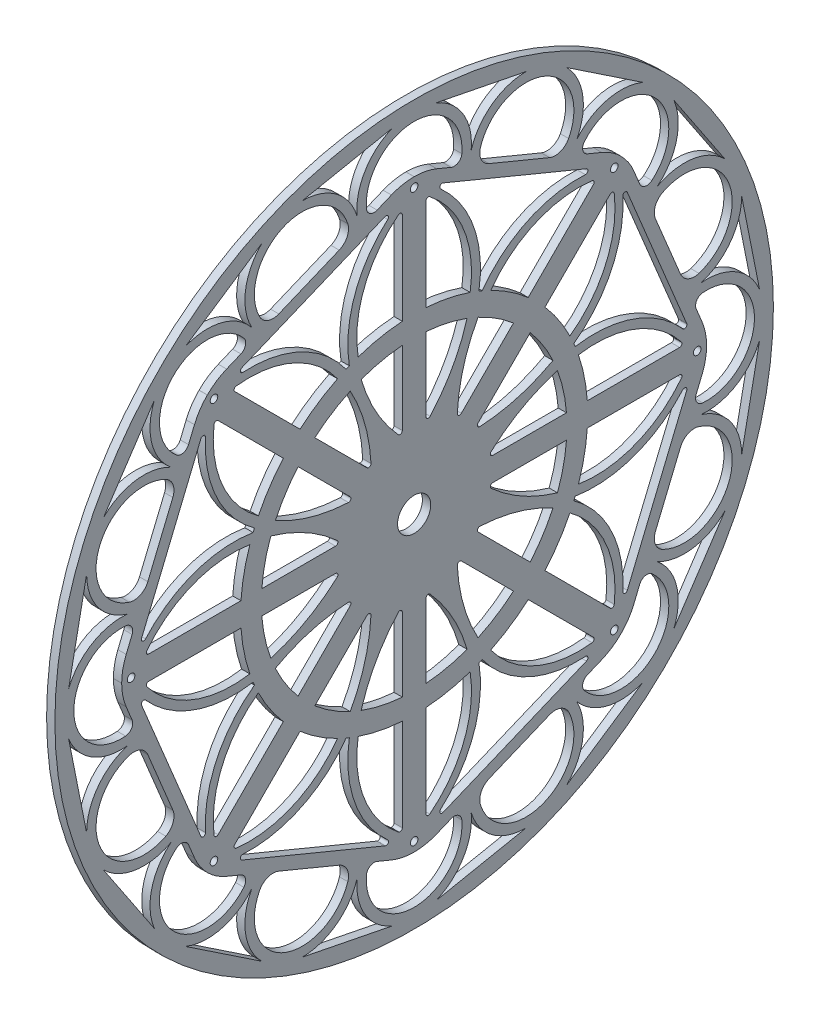
SolidWorks part; units mm, degrees
ref_plane "Front Plane" through (0, 0, 0) normal (1, 0, 0) x (0, 1, 0)
ref_plane "Top Plane" through (0, 0, 0) normal (0, 0, 1) x (0, 1, 0)
ref_plane "Right Plane" through (0, 0, 0) normal (0, 1, 0) x (-1, 0, 0)
sketch "Sketch1" plane through (0, 0, 0) normal (1, 0, 0) x (0, 1, 0)
  line L0 (0, 117.5907) -> (0, 0) construction
  line L1 (83.1492, 83.1492) -> (0, 117.5907) construction
  line L2 (0, 117.5907) -> (-83.1492, 83.1492) construction
  line L4 (-117.5907, 0) -> (-83.1492, -83.1492) construction
  line L5 (-83.1492, -83.1492) -> (0, -117.5907) construction
  line L6 (0, -117.5907) -> (83.1492, -83.1492) construction
  line L7 (83.1492, -83.1492) -> (117.5907, 0) construction
  line L8 (117.5907, 0) -> (83.1492, 83.1492) construction
  line L9 (-83.1492, 83.1492) -> (0, 0) construction
  line L10 (0, 0) -> (-117.5907, 0) construction
  line L11 (-117.5907, 0) -> (-118.1201, 0) construction
  line L12 (-123.5907, 0) -> (-123.5907, 5) construction
  line L14 (-36.2329, 29.1619) -> (-51.4539, 44.3828) construction
  line L15 (-90.9273, 83.8563) -> (-87.3918, 87.3918) construction
  line L16 (-87.3918, 87.3918) -> (-85.6448, 85.6448) construction
  line L18 (-121.1201, 0) -> (-123.5907, 0) construction
  line L19 (-123.5907, 5) -> (-90.9273, 83.8563) construction
  line L20 (-87.1005, 80.0294) -> (-118.1787, 5) construction
  line L21 (-55.2807, 48.2096) -> (-62.699, 30.3003) construction
  line L22 (-59.6103, 24.6914) -> (-36.2329, 29.1619) construction
  line L23 (-67.7667, 5) -> (-51.4539, 44.3828) construction
  line L24 (-59.6103, 24.6914) -> (-46.2411, 5) construction
  line L25 (0, 0) -> (-83.5235, 83.5235)
  line L26 (-55.2807, 48.2096) -> (-84.2721, 77.201) construction
  line L27 (-67.7667, 5) -> (-46.2411, 5) construction
  line L28 (-114.1787, 5) -> (-73.1787, 5) construction
  line L29 (-65.7604, 22.9093) -> (-73.1787, 5) construction
  line L30 (-85.6448, 85.6448) -> (-87.3918, 87.3918)
  line L31 (-83.1492, 83.1492) -> (-88.2348, 70.8713) construction
  line L32 (-87.3918, 87.3918) -> (-90.9273, 83.8563)
  line L33 (-90.9273, 83.8563) -> (-123.5907, 5)
  line L34 (-123.5907, 5) -> (-123.5907, 0)
  line L35 (-123.5907, 0) -> (-121.1201, 0)
  line L36 (-118.1201, 0) -> (0, 0)
  arc A0 (-108.6396, 0) -> (-76.8198, 76.8198) centre (0, 0) ccw construction
  arc A5 (-87.1005, 80.0294) -> (-64.2297, 26.6048) centre (-38.2585, 69.3307) ccw construction
  arc A6 (-114.1787, 5) -> (-65.7604, 22.9093) centre (-76.7606, -21.7561) cw construction
  arc A7 (-84.2721, 77.201) -> (-62.699, 30.3003) centre (-38.8941, 69.6618) ccw construction
  arc A8 (-118.1787, 5) -> (-64.2297, 26.6048) centre (-76.0771, -21.9713) cw construction
  arc A9 (-117.5907, 0) -> (-83.1492, 83.1492) centre (0, 0) ccw construction
  arc A12 (-85.6448, 85.6448) -> (-83.5235, 83.5235) centre (-84.5842, 84.5842) ccw
  arc A13 (-121.1201, 0) -> (-118.1201, 0) centre (-119.6201, 0) cw
  dimension "D1" = 6
  dimension "D8" = 50
  dimension "D9" = 4
  dimension "D12" = 46
  dimension "D13" = 4
  dimension "D4" = 1.5
  dimension "D11" = 1.5
  dimension "D2" = 90
  dimension "D3" = 5
  dimension "D5" = 5
  dimension "D7" = 5
  dimension "D10" = 45
extrude "Boss-Extrude3" add sketch "Sketch1" along normal blind 3.5
sketch "Sketch2" plane through (3.5, 0, 0) normal (1, 0, 0) x (0, 1, 0)
  line L0 (-84.2721, 77.201) -> (-55.2807, 48.2096)
  line L1 (-55.2807, 48.2096) -> (-62.699, 30.3003)
  line L2 (-65.7604, 22.9093) -> (-73.1787, 5)
  line L3 (-73.1787, 5) -> (-114.1787, 5)
  line L4 (-118.1787, 5) -> (-87.1005, 80.0294)
  arc A0 (-87.1005, 80.0294) -> (-64.2297, 26.6048) centre (-38.2585, 69.3307) ccw
  arc A1 (-62.699, 30.3003) -> (-84.2721, 77.201) centre (-38.8941, 69.6618) cw
  arc A2 (-64.2297, 26.6048) -> (-118.1787, 5) centre (-76.0771, -21.9713) ccw
  arc A3 (-65.7604, 22.9093) -> (-114.1787, 5) centre (-76.7606, -21.7561) ccw
extrude "Cut-Extrude5" cut sketch "Sketch2" against normal blind 3.5 contours A2 A0 L4 | A1 L1 L0 | L2 A3 L3 region at (3.5, -71.2812, 52.1242) region at (3.5, -87.2608, 13.5461) region at (3.5, -92.9106, 38.4849)
sketch "Sketch4" plane through (3.5, 0, 0) normal (1, 0, 0) x (0, 1, 0)
  line L0 (0, 0) -> (-83.5235, 83.5235) construction
  line L1 (-67.7667, 5) -> (-51.4539, 44.3828) construction
  line L2 (-118.1201, 0) -> (0, 0) construction
  line L3 (-58.6536, 27.0011) -> (-60.567, 22.3817) construction
  line L5 (-51.4539, 44.3828) -> (-25.2262, 18.1552)
  line L6 (-67.7667, 5) -> (-30.6753, 5)
  line L7 (-51.4539, 44.3828) -> (-58.6536, 27.0011)
  line L8 (-67.7667, 5) -> (-60.567, 22.3817)
  line L9 (-64.2297, 26.6048) -> (-59.6103, 24.6914) construction
  arc A0 (-18.3848, 18.3848) -> (-58.6536, 27.0011) centre (-24.2, 89.6145) cw construction
  arc A1 (-26, 0) -> (-60.567, 22.3817) centre (-80.479, -46.255) ccw construction
  arc A2 (-25.2262, 18.1552) -> (-58.6536, 27.0011) centre (-24.2, 89.6145) cw
  arc A3 (-60.567, 22.3817) -> (-30.6753, 5) centre (-80.479, -46.255) cw
  dimension "D1" = 26
  dimension "D2" = 26
  dimension "D3" = 5
  dimension "D4" = 5
extrude "Cut-Extrude6" cut sketch "Sketch4" against normal up to vertex (3.5 mm away) contours A2 L7 L5 | A3 L6 L8 up to point (0, -46.2411, 5)
fillet "Fillet3" radius 1 6 edges at (1.75, -118.1787, 5) (1.75, -87.1005, 80.0294) (1.75, -30.6753, 5) (1.75, -25.2262, 18.1552) (1.75, -114.1787, 5) (1.75, -84.2721, 77.201)
fillet "Fillet4" radius 25 2 edges at (1.75, -90.9273, 83.8563) (1.75, -123.5907, 5)
pattern_circular "CirPattern2" count 8 over 360 about axis through (3.5, 0, 0) along (-1, 0, 0) of "Boss-Extrude3", "Cut-Extrude5", "Cut-Extrude6", "Fillet3", "Fillet4"
sketch "Sketch5" plane through (3.5, 0, 0) normal (1, 0, 0) x (0, 0, -1)
  line L0 (0.0272, -123.5907) -> (0, -146.4823)
  line L1 (0, -146.4823) -> (0, -151.7532)
  line L2 (-87.411, -87.3726) -> (-103.6014, -103.5559)
  line L3 (-103.6014, -103.5559) -> (-107.3293, -107.2821)
  line L4 (-83.8563, -90.9273) -> (-5, -123.5907) construction
  line L5 (-62.7141, -99.6847) -> (-44.4281, -107.259) construction
  line L6 (-44.4281, -107.259) -> (-26.1422, -114.8333) construction
  line L7 (-87.411, -87.3726) -> (-62.7141, -99.6847) construction
  line L8 (-26.1422, -114.8333) -> (0.0272, -123.5907) construction
  line L9 (-103.6014, -103.5559) -> (-87.5988, -117.4032) construction
  line L10 (-21.1068, -144.9537) -> (0, -146.4823) construction
  circle A0 centre (0, 0) radius 151.7532 construction
  arc A1 (-107.3293, -107.2821) -> (0, -151.7532) centre (0, 0) ccw
  circle A2 centre (0, 0) radius 146.4823 construction
  arc A3 (-103.6014, -103.5559) -> (0, -146.4823) centre (0, 0) ccw
  arc A4 (-62.7141, -99.6847) -> (-103.6014, -103.5559) centre (-86.3933, -67.4466) cw
  arc A5 (-44.4281, -107.259) -> (-87.5988, -117.4032) centre (-73.2198, -81.6633) cw
  arc A6 (-26.1422, -114.8333) -> (0, -146.4823) centre (13.3992, -108.7933) ccw
  arc A7 (-44.4281, -107.259) -> (-21.1068, -144.9537) centre (-5.971, -109.5276) ccw
  dimension "D1" = 40
sketch "Sketch7" plane through (3.5, 0, 0) normal (1, 0, 0) x (0, 1, 0)
  line L0 (-90.9273, 83.8563) -> (-123.5907, 5) construction
  line L1 (-147.8187, 0) -> (-143.8187, 0)
  line L2 (-109.7756, 96.6635) -> (-131.3147, 64.4279)
  line L3 (-138.4109, 47.2961) -> (-145.9744, 9.2717)
  line L4 (-147.8187, 0) -> (-151.8187, 0)
  line L5 (-104.5236, 104.5236) -> (-107.352, 107.352)
  line L6 (-104.5236, 104.5236) -> (-101.6952, 101.6952)
  line L7 (-95.3376, 73.2089) -> (-101.9695, 57.198)
  line L8 (-119.1804, 15.6474) -> (-112.5485, 31.6582)
  circle A0 centre (0, 0) radius 123.5907 construction
  circle A1 centre (0, 0) radius 151.8187 construction
  arc A2 (-147.8187, 0) -> (-104.5236, 104.5236) centre (0, 0) ccw construction
  arc A3 (-68.6633, 102.7619) -> (-104.5236, 104.5236) centre (-87.3918, 87.3918) ccw construction
  arc A4 (-102.7619, 68.6633) -> (-131.3147, 64.4279) centre (-114.1829, 47.2961) ccw construction
  arc A5 (-121.2159, 24.1113) -> (-145.9744, 9.2717) centre (-123.5907, 0) ccw construction
  arc A6 (-102.7619, 68.6633) -> (-109.7756, 96.6635) centre (-87.3918, 87.3918) cw
  arc A7 (-102.7619, 68.6633) -> (-131.3147, 64.4279) centre (-114.1829, 47.2961) ccw
  arc A8 (-121.2159, 24.1113) -> (-145.9744, 9.2717) centre (-123.5907, 0) ccw
  arc A9 (-121.9353, 20.1602) -> (-143.8187, 0) centre (-123.5907, 0) ccw
  arc A10 (-100.4767, 71.9659) -> (-101.6952, 101.6952) centre (-87.3918, 87.3918) cw
  arc A11 (-104.9386, 65.2882) -> (-120.3685, 28.0371) centre (-114.1829, 47.2961) ccw
  arc A12 (-100.4767, 71.9659) -> (-95.3376, 73.2089) centre (-98.3603, 74.4609) ccw
  arc A13 (-104.9386, 65.2882) -> (-101.9695, 57.198) centre (-107.8449, 59.6317) cw
  arc A14 (-120.3685, 28.0371) -> (-112.5485, 31.6582) centre (-118.4238, 34.0919) ccw
  arc A15 (-121.9353, 20.1602) -> (-119.1804, 15.6474) centre (-122.2031, 16.8994) cw
  arc A16 (-107.352, 107.352) -> (-151.8187, 0) centre (0, 0) ccw
  arc A17 (-147.8187, 0) -> (-121.2159, -24.1113) centre (-123.5907, 0) ccw construction
  arc A18 (-138.4109, 47.2961) -> (-121.2159, 24.1113) centre (-114.1829, 47.2961) ccw construction
  arc A19 (-138.4109, 47.2961) -> (-121.2159, 24.1113) centre (-114.1829, 47.2961) ccw
  arc A20 (-109.7756, 96.6635) -> (-102.7619, 68.6633) centre (-87.3918, 87.3918) ccw construction
  dimension "D1" = 4
  dimension "D2" = 4
  dimension "D3" = 4
  dimension "D4" = 4
extrude "Boss-Extrude5" add sketch "Sketch7" against normal blind 3.5
sketch "Sketch8" plane through (3.5, 0, 0) normal (1, 0, 0) x (0, 0, -1)
  circle A0 centre (-84.5842, -84.5842) radius 1.6
  dimension "D1" = 3.2
extrude "Cut-Extrude7" cut sketch "Sketch8" against normal through all both and the other way through all
ref_axis "Axis3" through (-0.175, 0, 0) along (1, 0, 0)
pattern_circular "CirPattern4" count 8 over 360 about axis through (-0.175, 0, 0) along (1, 0, 0) of "Cut-Extrude7", "Boss-Extrude5"
sketch "Sketch9" plane through (0, 0, 0) normal (-1, 0, 0) x (0, 0, 1)
  circle A0 centre (0, 0) radius 64.5701
  circle A1 centre (0, 0) radius 73.3493
extrude "Boss-Extrude6" add sketch "Sketch9" against normal up to surface (3.5 mm away) up to face at (3.5, -119.6201, -1.6)
sketch "Sketch10" plane through (0, 0, 0) normal (-1, 0, 0) x (0, 0, 1)
  circle A0 centre (0, 0) radius 7
  dimension "D1" = 14
extrude "Cut-Extrude8" cut sketch "Sketch10" against normal blind 10
